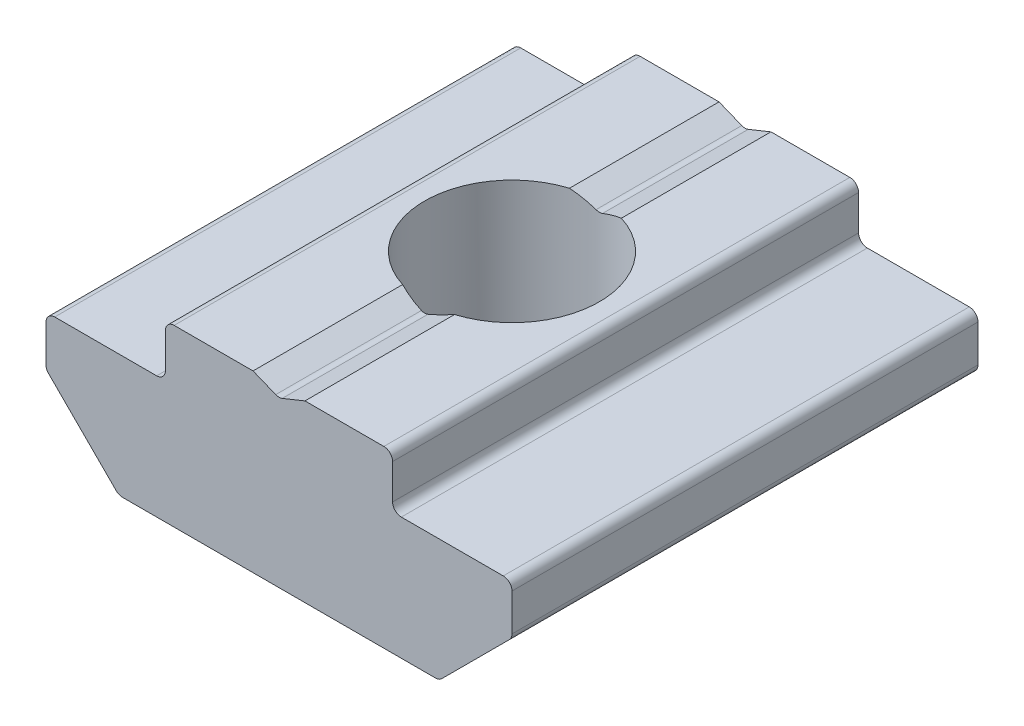
SolidWorks part; units mm, degrees
ref_plane "Front Plane" through (0, 0, 0) normal (0, 0, 1) x (1, 0, 0)
ref_plane "Top Plane" through (0, 0, 0) normal (0, 1, 0) x (1, 0, 0)
ref_plane "Right Plane" through (0, 0, 0) normal (1, 0, 0) x (0, 0, -1)
sketch "Sketch1" plane through (0, 0, 0) normal (0, 0, 1) x (1, 0, 0)
  line L0 (-8, 4.2) -> (8, 4.2) construction
  line L1 (0, 0) -> (0, 6) construction
  line L2 (-3.9, 6) -> (3.9, 6) construction
  line L3 (-3, 0) -> (3, 0) construction
  line L4 (3.1083, 0.0625) -> (2.2422, -0.4375) construction
  line L5 (2.2422, -0.4375) -> (3.1083, -0.9375) construction
  line L6 (3.1083, -0.9375) -> (3.1083, 0.0625) construction
  line L7 (2.3505, -0.375) -> (2.3505, -0.5) construction
  line L8 (3, 0) -> (3, -0.875) construction
  line L9 (3.0541, 0.0313) -> (3.0541, -0.9062) construction
  line L10 (3.1083, -0.4375) -> (3, -0.4375) construction
  line L11 (2.3505, -0.4375) -> (2.2422, -0.4375) construction
  line L13 (-0.891, 6) -> (0, 5.64) construction
  line L14 (0, 5.64) -> (0.891, 6) construction
  point P6 (0, 4.2)
  point P21 (3.0541, -0.4375)
  point P23 (0, 2.5)
  point P24 (8, 4.2)
  dimension "Overall Height" = 6
  dimension "Overall Length" = 16
  dimension "Head Length" = 7.8
  dimension "Hole Diameter" = 6
  dimension "Thread Pitch" = 1
  dimension "D2" = 0.125
  dimension "Head Height" = 1.8
  dimension "Undercut Height" = 2.5
  dimension "Cut Angle" = 136
  dimension "D1" = 0.36
sketch "Sketch2" plane through (0, 0, 0) normal (0, 1, 0) x (0, 0, -1)
  line L0 (-8, 0) -> (8, 0) construction
  line L1 (8, 8) -> (8, -8) construction
  line L2 (0, 8) -> (0, -8) construction
  line L3 (8, 8) -> (-8, 8) construction
  line L4 (-8, 8) -> (-8, 0) construction
  dimension "Width" = 16
sketch "Sketch4" plane through (0, 0, 0) normal (0, 0, 1) x (1, 0, 0)
  line L0 (-8, 4.2) -> (-8, 2.5)
  line L1 (-8, 2.5) -> (-5.5, 0)
  line L2 (-5.5, 0) -> (5.5, 0)
  line L3 (0, 0) -> (0, 6) construction
  line L4 (0, 0) -> (0, 4.2) construction
  line L7 (-8, 4.2) -> (8, 4.2) construction
  line L8 (8, 4.2) -> (3.9, 4.2)
  line L11 (8, 2.5) -> (5.5, 0)
  line L12 (8, 4.2) -> (8, 2.5)
  line L13 (0, 4.2) -> (0, 6) construction
  line L14 (-3.9, 4.2) -> (-3.9, 6)
  line L15 (-3.9, 6) -> (-0.891, 6)
  line L16 (3.9, 6) -> (3.9, 4.2)
  line L17 (-3.9, 4.2) -> (-8, 4.2)
  line L18 (0, 5.64) -> (-0.891, 6)
  line L21 (0.891, 6) -> (0, 5.64)
  line L22 (0.891, 6) -> (3.9, 6)
  dimension "D1" = 135
extrude "Boss-Extrude1" add sketch "Sketch4" along normal up to vertex (8 mm away) and the other way up to vertex (8 mm away) up to point (0, 0, 8) other way up to point (0, 0, -8)
sketch "Sketch17" plane through (2.25, 0, 0) normal (0, 1, 0) x (1, 0, 0)
  line L0 (-4.3713, -2.1213) -> (-2.25, 0) construction
  line L1 (-2.25, 0) -> (-2.25, -3) construction
  circle A0 centre (-2.25, 0) radius 3 construction
  dimension "D1" = 45
sketch "Sketch9" plane through (0, 0, 0) normal (0, 1, 0) x (1, 0, 0)
  circle A0 centre (0, 0) radius 3
extrude "Cut-Extrude2" cut sketch "Sketch9" along normal through all
fillet "Fillet1" radius 0.3 12 edges at (-3.9, 6, 0) (-3.9, 4.2, 0) (-8, 4.2, 0) (-8, 2.5, 0) (-5.5, 0, 0) (5.5, 0, 0) (8, 2.5, 0) (8, 4.2, 0) (3.9, 4.2, 0) (3.9, 6, 0) (0, 5.64, -5.5) (0, 5.64, 5.5)
ref_axis "Center Axis 1" through (0, 12.1219, 0) along (0, -1, 0)
ref_plane "Contact Plane 1" through (0, 4.2, 0) normal (0, 1, 0) x (1, 0, 0)
sketch "Sketch10" [suppressed] plane through (0, 0, 0) normal (0, 1, 0) x (1, 0, 0)
  circle A0 centre (0, 0) radius 3
curve "Helix/Spiral1" [suppressed] pitch 1 height 7 turns 7
sketch "Sketch12" [suppressed] plane through (0, 0, 0) normal (0, 0, 1) x (1, 0, 0)
  line L0 (3.0541, 0.0313) -> (3.0541, -0.9062)
  line L1 (3.0541, -0.9062) -> (2.3505, -0.5)
  line L2 (2.3505, -0.5) -> (2.3505, -0.375)
  line L3 (2.3505, -0.375) -> (3.0541, 0.0313)
sweep "Sweep1" [suppressed] add profiles "Sketch12" path "Helix/Spiral1"
sketch "Sketch13" [suppressed] plane through (0, 0, 0) normal (0, -1, 0) x (1, 0, 0)
  circle A0 centre (0, 0) radius 8
extrude "Cut-Extrude3" [suppressed] cut sketch "Sketch13" along normal through all
sketch "Sketch14" [suppressed] plane through (0, 6, 0) normal (0, 1, 0) x (1, 0, 0)
  circle A0 centre (0, 0) radius 8
extrude "Cut-Extrude4" [suppressed] cut sketch "Sketch14" along normal through all
sketch "Sketch15" [suppressed] plane through (0, 0, 0) normal (0, -1, 0) x (1, 0, 0)
  circle A1 centre (0, 0) radius 3
  circle A2 centre (0, 0) radius 3
  dimension "D1" = 0
extrude "Cut-Extrude5" [suppressed] cut sketch "Sketch15" against normal through all draft 45
sketch "Sketch16" [suppressed] plane through (0, 6, 0) normal (0, 1, 0) x (1, 0, 0)
  circle A1 centre (0, 0) radius 3
  circle A2 centre (0, 0) radius 3
  dimension "D1" = 0
extrude "Cut-Extrude6" [suppressed] cut sketch "Sketch16" against normal through all draft 45
sketch "Sketch18" [suppressed] plane through (0, 0, 0) normal (0, 0, 1) x (1, 0, 0)
  line L0 (-0.891, 6) -> (-0.1124, 5.6854)
  line L1 (-3.9, 6) -> (3.9, 6) construction
  line L2 (0, 0) -> (0, 6) construction
  line L3 (0.1124, 5.6854) -> (0.891, 6)
  line L4 (-0.891, 6) -> (0.891, 6)
  arc A0 (0.1124, 5.6854) -> (-0.1124, 5.6854) centre (0, 5.9636) cw
  point P12 (0, 5.64)
  dimension "D1" = 0.3
extrude "Cut-Extrude7" [suppressed] cut sketch "Sketch18" against normal through all both and the other way through all
ref_axis "NUT" through (0, 6.3, 0) along (0, -1, 0)
equation "\"D2@Sketch1\" = \"Thread Pitch@Sketch1\" / 8"
equation "\"D3@Helix/Spiral1\"=\"Overall Height@Sketch1\"+\"Thread Pitch@Sketch1\""
equation "\"D4@Helix/Spiral1\"=\"Thread Pitch@Sketch1\""
equation "\"D1@Sketch1\"=\"Head Height@Sketch1\"/5"
equation "\"D1@Sketch18\"=\"D1@Fillet1\""
